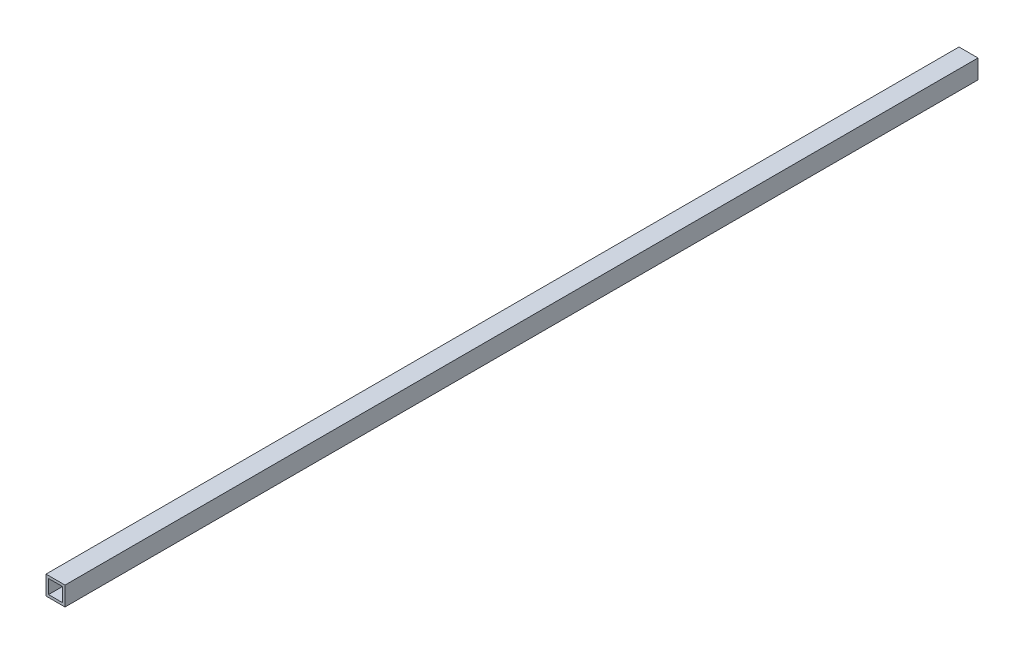
SolidWorks part; units mm, degrees
ref_plane "Front Plane" through (0, 0, 0) normal (0, 0, 1) x (1, 0, 0)
ref_plane "Top Plane" through (0, 0, 0) normal (0, 1, 0) x (1, 0, 0)
ref_plane "Right Plane" through (0, 0, 0) normal (1, 0, 0) x (0, 0, -1)
sketch "Sketch1" plane through (0, 0, 0) normal (0, 0, 1) x (1, 0, 0)
  line L0 (-4.65, 4.65) -> (4.65, 4.65)
  line L1 (-6.35, 6.35) -> (6.35, 6.35)
  line L2 (-6.35, 6.35) -> (-6.35, -6.35)
  line L3 (-6.35, -6.35) -> (6.35, -6.35)
  line L4 (6.35, 6.35) -> (6.35, -6.35)
  line L5 (-6.35, 6.35) -> (6.35, -6.35) construction
  line L6 (-6.35, -6.35) -> (6.35, 6.35) construction
  line L7 (4.65, 4.65) -> (4.65, -4.65)
  line L8 (-4.65, -4.65) -> (4.65, -4.65)
  line L9 (-4.65, 4.65) -> (-4.65, -4.65)
  point P0 (0, 0)
  dimension "D1" = 12.7
  dimension "D2" = 9.3
extrude "Boss-Extrude1" add sketch "Sketch1" along normal mid plane 609.6
ref_axis "Axis1" through (0, 0, 1005.84) along (0, 0, -1)
ref_plane "Plane1" through (0, 0, 0) normal (-0.7071, -0.7071, 0) x (-0.7071, 0.7071, 0)
